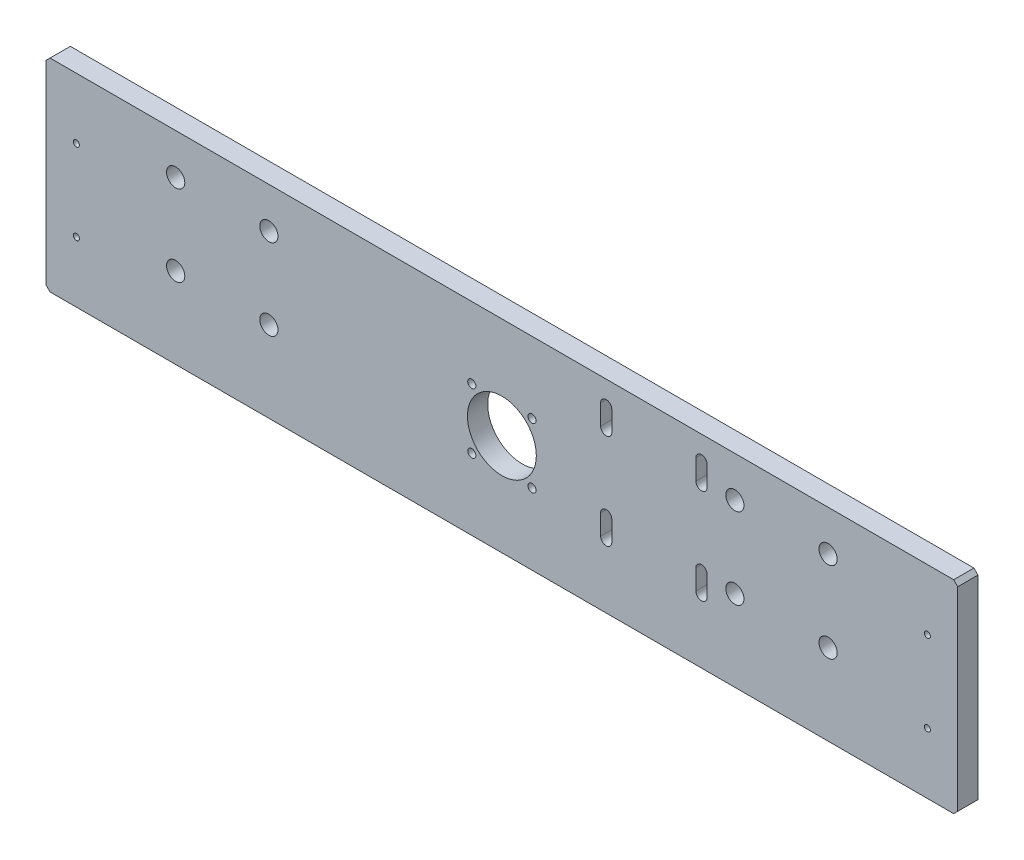
SolidWorks part; units mm, degrees
ref_plane "Piano frontale" through (0, 0, 0) normal (0, 0, 1) x (1, 0, 0)
ref_plane "Piano superiore" through (0, 0, 0) normal (0, 1, 0) x (1, 0, 0)
ref_plane "Piano destro" through (0, 0, 0) normal (1, 0, 0) x (0, 0, -1)
sketch "Schizzo1" plane through (0, 0, 0) normal (0, 0, 1) x (1, 0, 0)
  line L0 (225, 100) -> (225, 0) construction
  line L1 (2, 0) -> (448, 0)
  line L2 (0, 2) -> (0, 98)
  line L3 (2, 100) -> (448, 100)
  line L4 (450, 2) -> (450, 98)
  line L5 (87, 91.3578) -> (87, 40) construction
  line L7 (225, 50) -> (243.5099, 50) construction
  line L9 (225, 50) -> (205.51, 69.49) construction
  line L21 (0, 98) -> (2, 100)
  line L22 (2, 0) -> (0, 2)
  line L23 (448, 0) -> (450, 2)
  line L24 (448, 100) -> (450, 98)
  line L25 (225, 50) -> (450, 50) construction
  line L26 (316.3685, 60) -> (282.8483, 60) construction
  line L27 (323.5, 88.5) -> (323.5, 78.5) construction
  line L28 (320.75, 88.5) -> (320.75, 78.5)
  line L29 (326.25, 88.5) -> (326.25, 78.5)
  line L30 (276.5, 88.5) -> (276.5, 78.5) construction
  line L31 (279.25, 88.5) -> (279.25, 78.5)
  line L32 (273.75, 88.5) -> (273.75, 78.5)
  line L33 (323.5, 31.5) -> (323.5, 41.5) construction
  line L34 (320.75, 31.5) -> (320.75, 41.5)
  line L35 (326.25, 31.5) -> (326.25, 41.5)
  line L36 (276.5, 31.5) -> (276.5, 41.5) construction
  line L37 (279.25, 31.5) -> (279.25, 41.5)
  line L38 (273.75, 31.5) -> (273.75, 41.5)
  line L42 (300, 100) -> (300, 0) construction
  circle A0 centre (225, 50) radius 17
  circle A1 centre (225, 50) radius 21 construction
  circle A2 centre (239.8492, 64.8492) radius 2
  circle A3 centre (239.8492, 35.1508) radius 2
  circle A4 centre (210.1508, 35.1508) radius 2
  circle A11 centre (15, 30) radius 1.5
  circle A12 centre (435, 30) radius 1.5
  circle A13 centre (210.1508, 64.8492) radius 2
  circle A17 centre (435, 70) radius 1.5
  circle A18 centre (15, 70) radius 1.5
  arc A19 (320.75, 88.5) -> (326.25, 88.5) centre (323.5, 88.5) cw
  arc A20 (326.25, 78.5) -> (320.75, 78.5) centre (323.5, 78.5) cw
  arc A21 (279.25, 88.5) -> (273.75, 88.5) centre (276.5, 88.5) ccw
  arc A22 (273.75, 78.5) -> (279.25, 78.5) centre (276.5, 78.5) ccw
  arc A23 (320.75, 31.5) -> (326.25, 31.5) centre (323.5, 31.5) ccw
  arc A24 (326.25, 41.5) -> (320.75, 41.5) centre (323.5, 41.5) ccw
  arc A25 (279.25, 31.5) -> (273.75, 31.5) centre (276.5, 31.5) cw
  arc A26 (273.75, 41.5) -> (279.25, 41.5) centre (276.5, 41.5) cw
  circle A29 centre (110, 80) radius 4.5
  circle A30 centre (110, 40) radius 4.5
  circle A32 centre (64, 80) radius 4.5
  circle A33 centre (64, 40) radius 4.5
  circle A34 centre (386, 40) radius 4.5
  circle A35 centre (340, 40) radius 4.5
  circle A36 centre (340, 80) radius 4.5
  circle A37 centre (386, 80) radius 4.5
  point P0 (0, 0)
  point P1 (450, 100)
  point P2 (0, 100)
  point P3 (450, 0)
  point P9 (210.1508, 64.8492)
  point P13 (210.1508, 64.8492)
  point P80 (300, 60)
  point P83 (323.5, 83.5)
  point P90 (276.5, 83.5)
  point P97 (323.5, 36.5)
  point P104 (276.5, 36.5)
  dimension "D4" = 34
  dimension "D10" = 23
  dimension "D15" = 3
  dimension "D17" = 4
  dimension "D8" = 45
  dimension "D5" = 42
  dimension "D9" = 64
  dimension "D11" = 9
  dimension "D12" = 230
  dimension "D1" = 100
  dimension "D2" = 450
  dimension "D3" = 50
  dimension "D6" = 20
  dimension "D7" = 40
  dimension "D14" = 30
  dimension "D16" = 15
  dimension "D18" = 40
  dimension "D23" = 23.5
  dimension "D24" = 23.5
  dimension "D26" = 5.5
  dimension "D27" = 10
  dimension "D29" = 150
extrude "Boss-Extrude1" add sketch "Schizzo1" against normal blind 10
